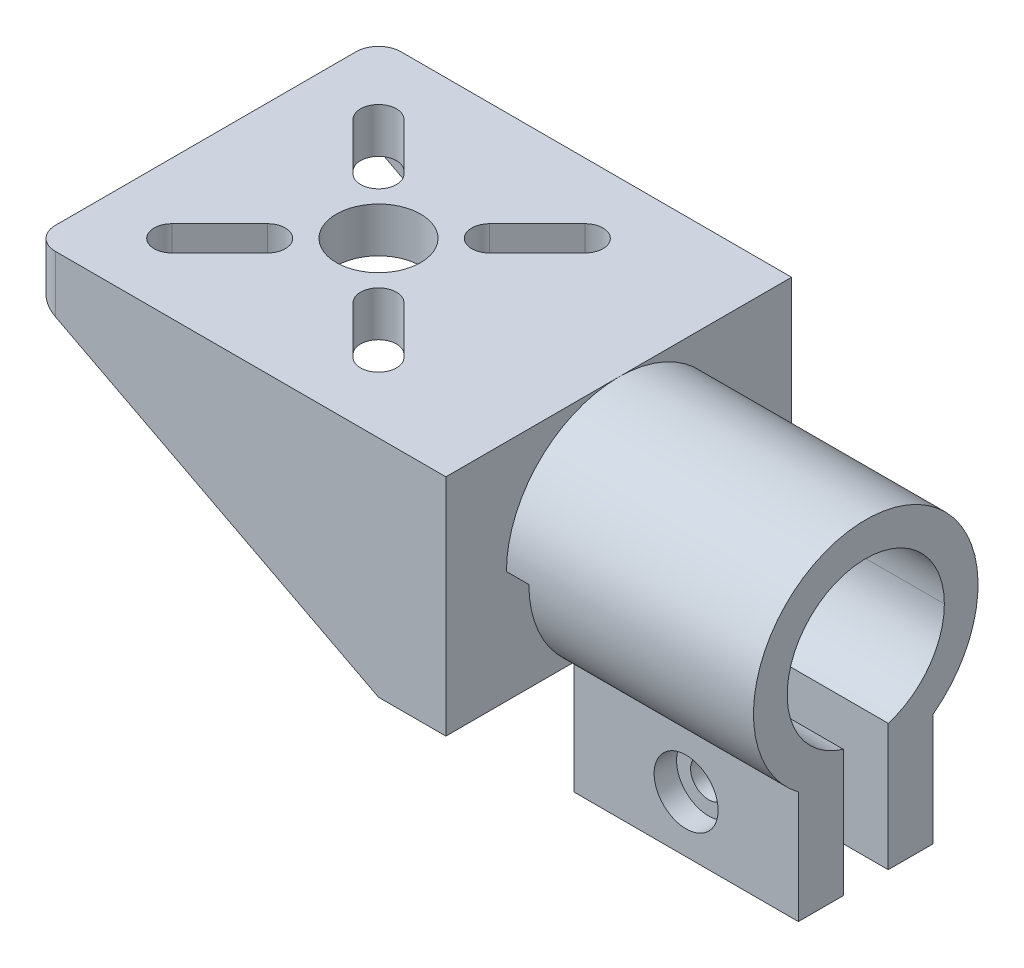
SolidWorks part; units mm, degrees
material "ABS"
ref_plane "Płaszczyzna przednia" through (0, 0, 0) normal (0, 0, 1) x (1, 0, 0)
ref_plane "Płaszczyzna górna" through (0, 0, 0) normal (0, 1, 0) x (1, 0, 0)
ref_plane "Płaszczyzna prawa" through (0, 0, 0) normal (1, 0, 0) x (0, 0, -1)
sketch "Szkic1" plane through (0, 0, 0) normal (0, 1, 0) x (1, 0, 0)
  line L0 (0, 0) -> (-4.9497, 4.9497) construction
  line L1 (-4.9497, 4.9497) -> (-9.1924, 9.1924) construction
  line L2 (-9.1924, 9.1924) -> (-4.9497, 4.9497) construction
  line L3 (-8.061, 10.3238) -> (-3.8184, 6.0811)
  line L4 (-10.3238, 8.061) -> (-6.0811, 3.8184)
  line L5 (9.1924, 9.1924) -> (4.9497, 4.9497) construction
  line L6 (10.3238, 8.061) -> (6.0811, 3.8184)
  line L7 (8.061, 10.3238) -> (3.8184, 6.0811)
  line L8 (9.1924, -9.1924) -> (4.9497, -4.9497) construction
  line L9 (8.061, -10.3238) -> (3.8184, -6.0811)
  line L10 (10.3238, -8.061) -> (6.0811, -3.8184)
  line L11 (-9.1924, -9.1924) -> (-4.9497, -4.9497) construction
  line L12 (-10.3238, -8.061) -> (-6.0811, -3.8184)
  line L13 (-8.061, -10.3238) -> (-3.8184, -6.0811)
  line L14 (0, 9) -> (0, -9) construction
  line L15 (-15.3924, 15.3924) -> (15.3924, 15.3924)
  line L16 (0, 0) -> (9.4723, 0) construction
  line L17 (-15.3924, -15.3924) -> (-15.3924, 15.3924)
  line L18 (15.3924, 15.3924) -> (15.3924, -15.3924)
  line L19 (15.3924, -15.3924) -> (-15.3924, -15.3924)
  circle A0 centre (0, 0) radius 3.75
  arc A10 (-8.061, 10.3238) -> (-10.3238, 8.061) centre (-9.1924, 9.1924) ccw
  arc A11 (-6.0811, 3.8184) -> (-3.8184, 6.0811) centre (-4.9497, 4.9497) ccw
  arc A12 (10.3238, 8.061) -> (8.061, 10.3238) centre (9.1924, 9.1924) ccw
  arc A13 (3.8184, 6.0811) -> (6.0811, 3.8184) centre (4.9497, 4.9497) ccw
  arc A14 (8.061, -10.3238) -> (10.3238, -8.061) centre (9.1924, -9.1924) ccw
  arc A15 (6.0811, -3.8184) -> (3.8184, -6.0811) centre (4.9497, -4.9497) ccw
  arc A16 (-10.3238, -8.061) -> (-8.061, -10.3238) centre (-9.1924, -9.1924) ccw
  arc A17 (-3.8184, -6.0811) -> (-6.0811, -3.8184) centre (-4.9497, -4.9497) ccw
  point P3 (-7.0711, 7.0711)
  point P13 (0, 0)
  point P14 (7.0711, 7.0711)
  point P21 (7.0711, -7.0711)
  point P22 (0, 0)
  point P29 (-7.0711, -7.0711)
  point P36 (0, 0)
  point P39 (0, -9)
  point P40 (0, 15.3924)
  point P41 (0, 0)
  point P45 (-15.3924, 0)
  point P46 (0, 0)
  dimension "D6" = 7.5
  dimension "D1" = 7
  dimension "D2" = 6
  dimension "D3" = 3.2
  dimension "D5" = 6.2
  dimension "D7" = 6.2
  dimension "D8" = 30.7848
  dimension "D4" = 4
extrude "Dodanie-wyciągnięcie1" add sketch "Szkic1" along normal blind 4
ref_plane "Płaszczyzna1" through (15.3924, 0, 0) normal (1, 0, 0) x (0, 0, -1)
sketch "Szkic2" plane through (15.3924, 0, 0) normal (1, 0, 0) x (0, 0, -1)
  line L1 (0, -13) -> (0, -16) construction
  line L2 (-15.3924, -16) -> (15.3924, -16)
  line L3 (15.3924, -16) -> (15.3924, 4)
  line L4 (-15.3924, -16) -> (-15.3924, 4)
  line L8 (0, 4) -> (0, 1) construction
  line L9 (-15.3924, 4) -> (15.3924, 4) construction
  line L10 (-15.3924, 4) -> (15.3924, 4)
  circle A0 centre (0, -6) radius 7
  point P9 (0, -16)
  point P10 (0, -16)
  point P19 (0, 4)
  dimension "D1" = 14
  dimension "D2" = 3
  dimension "D3" = 3
extrude "Dodanie-wyciągnięcie2" add sketch "Szkic2" along normal blind 4 contours A0 | L4 L2 L3 A0 region at (15.3924, -6, 15.0253) region at (15.3924, -6, 0)
ref_plane "Płaszczyzna2" through (-3.2736, -6.2986, 0) normal (-0.4612, -0.8873, 0) x (-0.8873, 0.4612, 0)
sketch "Szkic5" plane through (-3.2736, -6.2986, 0) normal (-0.4612, -0.8873, 0) x (-0.8873, 0.4612, 0)
  line L0 (13.6579, -15.3924) -> (-21.0366, -15.3924)
  line L1 (-21.0366, -15.3924) -> (-21.0366, -12.3924)
  line L2 (-21.0366, -15.3924) -> (-21.0366, 15.3924) construction
  line L3 (-21.0366, -12.3924) -> (13.6579, -12.3924)
  line L4 (13.6579, 15.3924) -> (13.6579, -15.3924) construction
  line L5 (13.6579, -12.3924) -> (13.6579, -15.3924)
  dimension "D1" = 3
extrude "Dodanie-wyciągnięcie3" add sketch "Szkic5" against normal up to next
mirror "Lustro1" about plane through (0, 0, 0) normal (0, 0, 1) of "Dodanie-wyciągnięcie3"
extrude "Dodanie-wyciągnięcie4" add sketch "Szkic2<3>" along normal blind 2 from surface starting at face at (19.3924, -6, 0)
sketch "Szkic2<3>" plane through (15.3924, 0, 0) normal (1, 0, 0) x (0, 0, -1) same geometry as "Szkic2"
fillet "Zaokrąglenie4" radius 2 2 edges at (-15.3924, 2, 15.3924) (-15.3924, 2, -15.3924)
sketch "Szkic6" plane through (21.3924, 0, 0) normal (1, 0, 0) x (0, 0, -1)
  line L0 (-10, -6) -> (-7, -6)
  line L1 (-7, -6) -> (7, -6) construction
  line L2 (7, -6) -> (10, -6)
  line L3 (0, 4) -> (0, 1) construction
  line L4 (-15.3924, 4) -> (15.3924, 4) construction
  arc A0 (7, -6) -> (-7, -6) centre (0, -6) ccw
  arc A1 (10, -6) -> (-10, -6) centre (0, -6) ccw
  dimension "D3" = 3
  dimension "D2" = 7
extrude "Dodanie-wyciągnięcie5" add sketch "Szkic6" along normal blind 2
sketch "Szkic7" plane through (23.3924, 0, 0) normal (1, 0, 0) x (0, 0, -1)
  line L0 (0, -6) -> (0, -24) construction
  line L2 (2, -24) -> (2, -12.7082)
  line L3 (2, -24) -> (6, -24)
  line L4 (6, -24) -> (6, -14)
  line L5 (-2, -24) -> (-2, -12.7082)
  line L6 (-2, -24) -> (-6, -24)
  line L7 (-6, -24) -> (-6, -14)
  arc A0 (2, -12.7082) -> (-2, -12.7082) centre (0, -6) ccw
  arc A1 (6, -14) -> (-6, -14) centre (0, -6) ccw
  arc A2 (-2, -12.7082) -> (0, -13) centre (0, -6) ccw construction
  arc A3 (-2, -15.798) -> (0, -16) centre (0, -6) ccw construction
  arc A4 (0, -13) -> (2, -12.7082) centre (0, -6) ccw
  arc A5 (0, -16) -> (2, -15.798) centre (0, -6) ccw
  arc A6 (-6, -14) -> (-2, -15.798) centre (0, -6) ccw construction
  arc A7 (2, -15.798) -> (6, -14) centre (0, -6) ccw construction
  point P9 (0, -24)
  arc M3 (10, -6) -> (-10, -6) centre (0, -6) ccw
  line M4 (-10, -6) -> (-7, -6)
  arc M5 (-7, -6) -> (7, -6) centre (0, -6) cw
  line M6 (7, -6) -> (10, -6)
  dimension "D6" = 7
  dimension "D1" = 4
  dimension "D2" = 4
  dimension "D3" = 4
  dimension "D4" = 18
  dimension "D5" = 3
  dimension "D7" = 2
extrude "Dodanie-wyciągnięcie6" add sketch "Szkic7" along normal blind 20 contours M6 M3 M4 M5 | A1 L7 L6 L5 A0 M4 | L4 A1 A0 L2 L3 M6 region at (23.3924, -15.3369, -5.1379) region at (23.3924, 1.2236, 0) region at (23.3924, -15.3369, 5.1379)
sketch "Szkic8" plane through (19.3924, 0, 0) normal (1, 0, 0) x (0, 0, -1)
  line L0 (-4.9, -5.9447) -> (4.9, -5.9447) construction
  line L1 (4.9, -9.4447) -> (4.9, -2.4447)
  line L2 (4.9, -2.4447) -> (-4.9, -2.4447)
  line L3 (-4.9, -9.4447) -> (-4.9, -2.4447)
  line L4 (-4.9, -9.4447) -> (4.9, -9.4447)
  line L5 (0, 0) -> (0, -14.6269) construction
  point P4 (0, -5.9447)
  point P7 (4.9, -5.9447)
  point P11 (-4.9, -5.9447)
  dimension "D2" = 7
  dimension "D1" = 9.8
extrude "Wytnij-wyciągnięcie1" cut sketch "Szkic8" against normal up to next
fillet "Zaokrąglenie5" radius 4 4 edges at (17.3924, -2.4447, 4.9) (17.3924, -2.4447, -4.9) (17.3924, -9.4447, -4.9) (17.3924, -9.4447, 4.9)
sketch "Szkic9" plane through (0, 0, 6) normal (0, 0, 1) x (1, 0, 0)
  line L0 (23.3924, -19) -> (43.3924, -19) construction
  line L1 (23.3924, -24) -> (43.3924, -24) construction
  line L2 (23.3924, -24) -> (23.3924, -14) construction
  line L3 (23.3924, -14) -> (43.3924, -14) construction
  line L4 (43.3924, -24) -> (43.3924, -14) construction
  circle A0 centre (33.3924, -19) radius 1.6
  dimension "D1" = 3.2
extrude "Wytnij-wyciągnięcie2" cut sketch "Szkic9" against normal up to surface (12 mm away) up to face at (33.3924, -19, -6)
sketch "Szkic10" plane through (0, 0, 6) normal (0, 0, 1) x (1, 0, 0)
  circle A0 centre (33.3924, -19) radius 2.85
  dimension "D1" = 5.7
extrude "Wytnij-wyciągnięcie3" cut sketch "Szkic10" against normal blind 2
sketch "Szkic11" plane through (0, 0, -6) normal (0, 0, -1) x (-1, 0, 0)
  line L1 (-36.6833, -19) -> (-35.0378, -21.85)
  line L2 (-35.0378, -21.85) -> (-31.7469, -21.85)
  line L3 (-31.7469, -21.85) -> (-30.1015, -19)
  line L4 (-30.1015, -19) -> (-31.7469, -16.15)
  line L5 (-31.7469, -16.15) -> (-35.0378, -16.15)
  line L6 (-35.0378, -16.15) -> (-36.6833, -19)
  circle A0 centre (-33.3924, -19) radius 2.85 construction
  dimension "D1" = 5.7
extrude "Wytnij-wyciągnięcie4" cut sketch "Szkic11" against normal blind 2
equation "\"Diameter\"=14"
equation "\"WallThickness\"= 3"
equation "\"D5@Szkic1\"=0.2 +\"WallThickness\"*2"
equation "\"D7@Szkic1\"=0.2 +\"WallThickness\"*2"
equation "\"D2@Szkic2\"=\"WallThickness\""
equation "\"D1@Szkic5\"=\"WallThickness\""
equation "\"Tolerance\"= 0.1"
equation "\"SkrewGap\"= 4"
equation "\"SkrewWallThickness\"= 4"
equation "\"SkrewLength\"= 8"
equation "\"D1@Szkic7\"=\"SkrewGap\""
equation "\"D2@Szkic7\"=\"SkrewWallThickness\""
equation "\"D3@Szkic7\"=\"SkrewWallThickness\""
equation "\"D4@Szkic7\"=\"Diameter\"/2 +\"WallThickness\" +\"SkrewLength\""
equation "\"D5@Szkic7\"=\"WallThickness\""
equation "\"D3@Szkic2\"=\"WallThickness\""
equation "\"D2@Szkic6\"=\"Diameter\"/2"
equation "\"D3@Szkic6\"=\"WallThickness\""
equation "\"D6@Szkic7\"=\"Diameter\"/2"
equation "\"D7@Szkic7\"=\"SkrewGap\"/2"
equation "\"D1@Szkic6\"=\"WallThickness\""
equation "\"D1@Szkic2\"=\"Diameter\""
equation "\"D1@Szkic8\"=\"Diameter\"*0.7"
equation "\"D2@Szkic8\"=\"Diameter\"*0.5"
equation "\"D1@Szkic9\"=3 +\"Tolerance\"*2"
equation "\"D1@Szkic10\"=5.5 +\"Tolerance\"*2"
equation "\"D1@Wytnij-wyciągnięcie3\"=\"SkrewWallThickness\"/2"
equation "\"D1@Szkic11\"=5.5 +\"Tolerance\"*2"
equation "\"D1@Wytnij-wyciągnięcie4\"=\"SkrewWallThickness\"/2"
